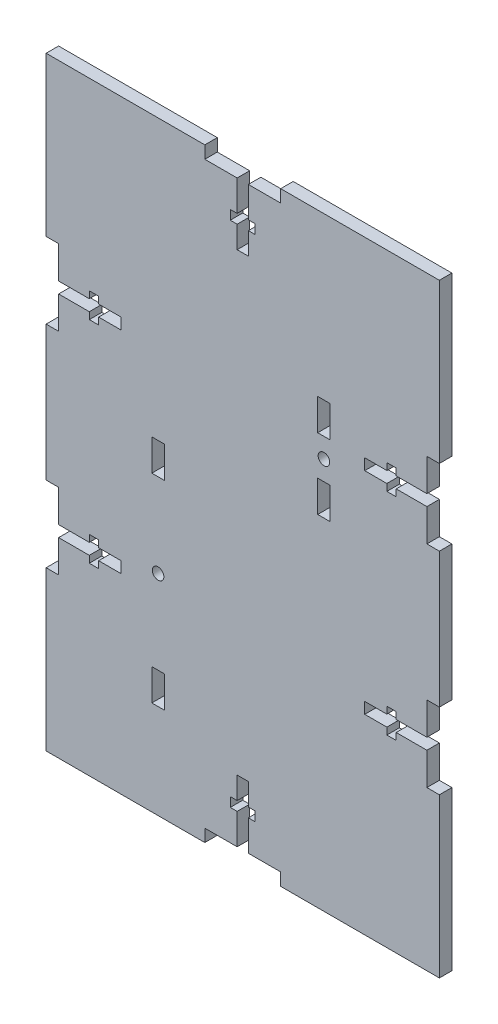
SolidWorks part; units mm, degrees
ref_plane "Front Plane" through (0, 0, 0) normal (0, 0, 1) x (1, 0, 0)
ref_plane "Top Plane" through (0, 0, 0) normal (0, 1, 0) x (1, 0, 0)
ref_plane "Right Plane" through (0, 0, 0) normal (1, 0, 0) x (0, 0, -1)
sketch "Sketch1" plane through (0, 0, 0) normal (0, 0, 1) x (1, 0, 0)
  line L0 (-50, 76.825) -> (-16.6667, 76.825)
  line L1 (-50, -76.825) -> (50, -76.825)
  line L2 (-50, -76.825) -> (-50, 76.825)
  line L3 (-50, 76.825) -> (50, 76.825) construction
  line L4 (50, -76.825) -> (50, 76.825)
  line L5 (-50, -76.825) -> (50, 76.825) construction
  line L6 (-50, 76.825) -> (50, -76.825) construction
  line L7 (-16.6667, 76.825) -> (16.6667, 76.825)
  line L8 (16.6667, 76.825) -> (50, 76.825)
  point P0 (0, 0)
  dimension "D1" = 100
  dimension "D2" = 153.65
extrude "Boss-Extrude1" add sketch "Sketch1" along normal blind 3.18
sketch "Sketch3" [suppressed] plane through (0, 0, 0) normal (0, 0, -1) x (-1, 0, 0)
  line L0 (-32.675, 34.075) -> (-32.675, -61.675)
  line L1 (-32.675, -61.675) -> (32.675, -61.675)
  line L2 (32.675, -61.675) -> (32.675, 34.075)
  line L3 (32.675, 34.075) -> (9.5, 34.075)
  line L4 (9.5, 34.075) -> (9.5, 37.075)
  line L5 (9.5, 37.075) -> (-9.5, 37.075)
  line L6 (-9.5, 37.075) -> (-9.5, 34.075)
  line L7 (-9.5, 34.075) -> (-32.675, 34.075)
  line L8 (32.675, 44.075) -> (-32.675, 44.075)
  line L9 (32.675, -61.675) -> (32.675, 44.075)
  line L10 (-32.675, -61.675) -> (32.675, -61.675)
  line L11 (-32.675, 44.075) -> (-32.675, -61.675)
  line L12 (-32.675, -61.675) -> (-32.675, -73.645) construction
  line L13 (44.645, -73.645) -> (-44.645, -73.645) construction
  line L14 (-32.675, -61.675) -> (-44.645, -61.675) construction
  line L15 (-44.645, -73.645) -> (-44.645, 73.645) construction
  line L16 (32.675, -61.675) -> (44.645, -61.675) construction
  line L17 (44.645, 73.645) -> (44.645, -73.645) construction
  dimension "D1" = 65.35
  dimension "D2" = 95.75
  dimension "D3" = 105.75
  dimension "D4" = 19
  dimension "D5" = 3
extrude "Cut-Extrude1" [suppressed] cut sketch "Sketch3" against normal through all contours L6 L7 L0 L1 L2 L3 L4 L5
sketch "Sketch9" [suppressed] plane through (-44.645, 0, 0) normal (-1, 0, 0) x (0, 0, 1)
  line L0 (0, 0) -> (3.18, 0) construction
  line L1 (0, 50) -> (0, -50) construction
  line L2 (3.18, 50) -> (3.18, -50) construction
  line L4 (0, -9.65) -> (3.18, -9.65)
  line L5 (0, -9.65) -> (0, 9.65)
  line L6 (0, 9.65) -> (3.18, 9.65)
  line L7 (3.18, -9.65) -> (3.18, 9.65)
  line L8 (0, -9.65) -> (3.18, 9.65) construction
  line L9 (0, 9.65) -> (3.18, -9.65) construction
  point P6 (1.59, 0)
  dimension "D1" = 19.3
extrude "Boss-Extrude4" [suppressed] add sketch "Sketch9" along normal blind 3.18
sketch "Sketch10" [suppressed] plane through (0, 0, 3.18) normal (0, 0, 1) x (1, 0, 0)
  line L0 (-46.235, 9.65) -> (-46.235, -9.65) construction
  line L1 (-47.825, 9.65) -> (-44.645, 9.65) construction
  line L2 (-47.825, -9.65) -> (-44.645, -9.65) construction
  circle A0 centre (-46.235, 0) radius 1.425
extrude "Cut-Extrude4" [suppressed] cut sketch "Sketch10" against normal through all
mirror "Mirror1" [suppressed] about plane through (0, 0, 0) normal (1, 0, 0)
sketch "Sketch18" [suppressed] plane through (44.645, 0, 0) normal (1, 0, 0) x (0, 0, -1)
  line L0 (0, 0) -> (-3.18, 0) construction
  line L1 (0, -50) -> (0, 50) construction
  line L2 (-3.18, -50) -> (-3.18, 50) construction
  line L4 (-3.18, -9.65) -> (0, -9.65)
  line L5 (-3.18, -9.65) -> (-3.18, 9.65)
  line L6 (-3.18, 9.65) -> (0, 9.65)
  line L7 (0, -9.65) -> (0, 9.65)
  line L8 (-3.18, -9.65) -> (0, 9.65) construction
  line L9 (-3.18, 9.65) -> (0, -9.65) construction
  point P6 (-1.59, 0)
  dimension "D1" = 19.3
extrude "Boss-Extrude8" [suppressed] add sketch "Sketch18" along normal blind 3.18
sketch "Sketch19" [suppressed] plane through (0, 0, 3.18) normal (0, 0, 1) x (1, 0, 0)
  line L0 (46.235, -9.65) -> (46.235, 9.65) construction
  line L1 (47.825, -9.65) -> (44.645, -9.65) construction
  line L2 (47.825, 9.65) -> (44.645, 9.65) construction
  circle A0 centre (46.235, 0) radius 1.425
extrude "Cut-Extrude8" [suppressed] cut sketch "Sketch19" against normal through all
mirror "Mirror2" [suppressed] about plane through (0, 0, 0) normal (1, 0, 0)
sketch "Sketch20" plane through (0, 0, 3.18) normal (0, 0, 1) x (1, 0, 0)
  line L0 (0, 70.465) -> (0, 0) construction
  line L1 (50, 76.825) -> (-50, 76.825) construction
  line L2 (-9.65, 76.825) -> (9.65, 76.825)
  line L3 (9.65, 76.825) -> (9.65, 73.645)
  line L4 (9.65, 73.645) -> (1.425, 73.645)
  line L5 (1.425, 73.645) -> (1.425, 65.845)
  line L6 (1.425, 65.845) -> (3.175, 65.845)
  line L7 (3.175, 65.845) -> (3.175, 63.465)
  line L8 (3.175, 63.465) -> (1.425, 63.465)
  line L9 (1.425, 63.465) -> (1.425, 57.845)
  line L10 (1.425, 57.845) -> (-1.425, 57.845)
  line L11 (-1.425, 57.845) -> (-1.425, 63.465)
  line L12 (-1.425, 63.465) -> (-3.175, 63.465)
  line L13 (-3.175, 63.465) -> (-3.175, 65.845)
  line L14 (-3.175, 65.845) -> (-1.425, 65.845)
  line L15 (-1.425, 65.845) -> (-1.425, 73.645)
  line L16 (-1.425, 73.645) -> (-9.65, 73.645)
  line L17 (-9.65, 73.645) -> (-9.65, 76.825)
  dimension "D1" = 19.3
  dimension "D2" = 3.18
  dimension "D3" = 15.8
  dimension "D4" = 6.35
  dimension "D5" = 2.38
  dimension "D6" = 2.85
  dimension "D7" = 7.8
extrude "Cut-Extrude9" cut sketch "Sketch20" against normal through all
mirror "Mirror3" about plane through (0, 0, 0) normal (0, 1, 0) of "Cut-Extrude9"
sketch "Sketch23" plane through (0, 0, 3.18) normal (0, 0, 1) x (1, 0, 0)
  line L0 (-50, 17.175) -> (-50, 36.475)
  line L1 (-50, 76.825) -> (-50, -76.825) construction
  line L2 (-50, 36.475) -> (-46.82, 36.475)
  line L3 (-46.82, 36.475) -> (-46.82, 28.25)
  line L4 (-46.82, 28.25) -> (-39.02, 28.25)
  line L5 (-39.02, 28.25) -> (-39.02, 30)
  line L6 (-39.02, 30) -> (-36.64, 30)
  line L7 (-36.64, 30) -> (-36.64, 28.25)
  line L8 (-36.64, 28.25) -> (-31.02, 28.25)
  line L9 (-31.02, 28.25) -> (-31.02, 25.4)
  line L10 (-31.02, 25.4) -> (-36.64, 25.4)
  line L11 (-36.64, 25.4) -> (-36.64, 23.65)
  line L12 (-36.64, 23.65) -> (-39.02, 23.65)
  line L13 (-39.02, 23.65) -> (-39.02, 25.4)
  line L14 (-39.02, 25.4) -> (-46.82, 25.4)
  line L15 (-46.82, 25.4) -> (-46.82, 17.175)
  line L16 (-46.82, 17.175) -> (-50, 17.175)
  line L17 (-9.65, 76.825) -> (-50, 76.825) construction
  line L19 (-31.02, 26.825) -> (-50, 26.825) construction
  line L20 (-50, -36.475) -> (-50, -17.175)
  line L21 (-50, -17.175) -> (-46.82, -17.175)
  line L22 (-46.82, -17.175) -> (-46.82, -25.4)
  line L23 (-46.82, -25.4) -> (-39.02, -25.4)
  line L24 (-39.02, -25.4) -> (-39.02, -23.65)
  line L25 (-39.02, -23.65) -> (-36.64, -23.65)
  line L26 (-36.64, -23.65) -> (-36.64, -25.4)
  line L27 (-36.64, -25.4) -> (-31.02, -25.4)
  line L28 (-31.02, -25.4) -> (-31.02, -28.25)
  line L29 (-31.02, -28.25) -> (-36.64, -28.25)
  line L30 (-36.64, -28.25) -> (-36.64, -30)
  line L31 (-36.64, -30) -> (-39.02, -30)
  line L32 (-39.02, -30) -> (-39.02, -28.25)
  line L33 (-39.02, -28.25) -> (-46.82, -28.25)
  line L34 (-46.82, -28.25) -> (-46.82, -36.475)
  line L35 (-46.82, -36.475) -> (-50, -36.475)
  line L36 (-50, -26.825) -> (-31.02, -26.825) construction
  line L37 (-50, -76.825) -> (-9.65, -76.825) construction
  dimension "D1" = 50
  dimension "D2" = 19.3
  dimension "D3" = 3.18
  dimension "D4" = 15.8
  dimension "D5" = 6.35
  dimension "D6" = 2.85
  dimension "D7" = 7.8
  dimension "D8" = 2.38
  dimension "D9" = 19.3
  dimension "D10" = 3.18
  dimension "D11" = 7.8
  dimension "D12" = 15.8
  dimension "D13" = 6.35
  dimension "D14" = 2.85
  dimension "D15" = 2.38
  dimension "D16" = 50
  dimension "D17" = 1.75
extrude "Cut-Extrude10" cut sketch "Sketch23" against normal through all
sketch "Sketch24" [suppressed] plane through (0, 0, 3.18) normal (0, 0, 1) x (1, 0, 0)
  line L0 (50, -17.175) -> (50, -36.475)
  line L1 (50, -76.825) -> (50, 76.825) construction
  line L2 (50, -36.475) -> (46.82, -36.475)
  line L3 (46.82, -36.475) -> (46.82, -28.25)
  line L4 (46.82, -28.25) -> (39.02, -28.25)
  line L5 (39.02, -28.25) -> (39.02, -30)
  line L6 (39.02, -30) -> (36.64, -30)
  line L7 (36.64, -30) -> (36.64, -28.25)
  line L8 (36.64, -28.25) -> (31.02, -28.25)
  line L9 (31.02, -28.25) -> (31.02, -25.4)
  line L10 (31.02, -25.4) -> (36.64, -25.4)
  line L11 (36.64, -25.4) -> (36.64, -23.65)
  line L12 (36.64, -23.65) -> (39.02, -23.65)
  line L13 (39.02, -23.65) -> (39.02, -25.4)
  line L14 (39.02, -25.4) -> (46.82, -25.4)
  line L15 (46.82, -25.4) -> (46.82, -17.175)
  line L16 (46.82, -17.175) -> (50, -17.175)
  line L17 (31.02, -26.825) -> (50, -26.825) construction
  line L18 (9.65, -76.825) -> (50, -76.825) construction
  line L19 (50, 36.475) -> (50, 17.175)
  line L20 (50, 17.175) -> (46.82, 17.175)
  line L21 (46.82, 17.175) -> (46.82, 25.4)
  line L22 (46.82, 25.4) -> (39.02, 25.4)
  line L23 (39.02, 25.4) -> (39.02, 23.65)
  line L24 (39.02, 23.65) -> (36.64, 23.65)
  line L25 (36.64, 23.65) -> (36.64, 25.4)
  line L26 (36.64, 25.4) -> (31.02, 25.4)
  line L27 (31.02, 25.4) -> (31.02, 28.25)
  line L28 (31.02, 28.25) -> (36.64, 28.25)
  line L29 (36.64, 28.25) -> (36.64, 30)
  line L30 (36.64, 30) -> (39.02, 30)
  line L31 (39.02, 30) -> (39.02, 28.25)
  line L32 (39.02, 28.25) -> (46.82, 28.25)
  line L33 (46.82, 28.25) -> (46.82, 36.475)
  line L34 (46.82, 36.475) -> (50, 36.475)
  line L35 (31.02, 26.825) -> (50, 26.825) construction
  line L36 (50, 76.825) -> (9.65, 76.825) construction
  dimension "D1" = 19.3
  dimension "D2" = 3.18
  dimension "D3" = 15.8
  dimension "D4" = 7.8
  dimension "D5" = 6.35
  dimension "D6" = 2.85
  dimension "D7" = 2.38
  dimension "D8" = 50
  dimension "D9" = 19.3
  dimension "D10" = 3.18
  dimension "D11" = 7.8
  dimension "D12" = 15.8
  dimension "D13" = 6.35
  dimension "D14" = 2.85
  dimension "D15" = 2.38
  dimension "D16" = 50
extrude "Cut-Extrude11" [suppressed] cut sketch "Sketch24" against normal through all
sketch "Sketch25" [suppressed] plane through (0, 0, 3.18) normal (0, 0, 1) x (1, 0, 0)
  line L0 (9.65, -50) -> (-9.65, -50)
  line L1 (-44.645, -50) -> (44.645, -50) construction
  line L2 (-9.65, -50) -> (-9.65, -46.82)
  line L3 (-9.65, -46.82) -> (-1.425, -46.82)
  line L4 (-1.425, -46.82) -> (-1.425, -39.02)
  line L5 (-1.425, -39.02) -> (-3.175, -39.02)
  line L6 (-3.175, -39.02) -> (-3.175, -36.64)
  line L7 (-3.175, -36.64) -> (-1.425, -36.64)
  line L8 (-1.425, -36.64) -> (-1.425, -31.02)
  line L9 (-1.425, -31.02) -> (1.425, -31.02)
  line L10 (1.425, -31.02) -> (1.425, -36.64)
  line L11 (1.425, -36.64) -> (3.175, -36.64)
  line L12 (3.175, -36.64) -> (3.175, -39.02)
  line L13 (3.175, -39.02) -> (1.425, -39.02)
  line L14 (1.425, -39.02) -> (1.425, -46.82)
  line L15 (1.425, -46.82) -> (9.65, -46.82)
  line L16 (9.65, -46.82) -> (9.65, -50)
  line L17 (0, -50) -> (0, 0) construction
  dimension "D1" = 19.3
  dimension "D2" = 3.18
  dimension "D3" = 15.8
  dimension "D4" = 7.8
  dimension "D5" = 6.35
  dimension "D6" = 2.85
  dimension "D7" = 2.38
extrude "Cut-Extrude12" [suppressed] cut sketch "Sketch25" against normal through all
sketch "Sketch26" [suppressed] plane through (0, 0, 3.18) normal (0, 0, 1) x (1, 0, 0)
  line L0 (-9.65, 50) -> (9.65, 50)
  line L1 (44.645, 50) -> (-44.645, 50) construction
  line L2 (9.65, 50) -> (9.65, 46.82)
  line L3 (9.65, 46.82) -> (1.425, 46.82)
  line L4 (1.425, 46.82) -> (1.425, 39.02)
  line L5 (1.425, 39.02) -> (3.175, 39.02)
  line L6 (3.175, 39.02) -> (3.175, 36.64)
  line L7 (3.175, 36.64) -> (1.425, 36.64)
  line L8 (1.425, 36.64) -> (1.425, 31.02)
  line L9 (1.425, 31.02) -> (-1.425, 31.02)
  line L10 (-1.425, 31.02) -> (-1.425, 36.64)
  line L11 (-1.425, 36.64) -> (-3.175, 36.64)
  line L12 (-3.175, 36.64) -> (-3.175, 39.02)
  line L13 (-3.175, 39.02) -> (-1.425, 39.02)
  line L14 (-1.425, 39.02) -> (-1.425, 46.82)
  line L15 (-1.425, 46.82) -> (-9.65, 46.82)
  line L16 (-9.65, 46.82) -> (-9.65, 50)
  line L17 (0, 50) -> (0, -4.4192) construction
  dimension "D1" = 19.3
  dimension "D2" = 3.18
  dimension "D3" = 7.8
  dimension "D4" = 15.8
  dimension "D5" = 6.35
  dimension "D6" = 2.85
  dimension "D7" = 2.38
extrude "Cut-Extrude13" [suppressed] cut sketch "Sketch26" against normal through all
mirror "Mirror4" about plane through (0, 0, 0) normal (1, 0, 0) of "Cut-Extrude10"
mirror "Mirror5" [suppressed] about plane through (0, 0, 0) normal (1, 0, 0)
mirror "Mirror6" [suppressed] about plane through (0, 0, 0) normal (0, 1, 0)
mirror "Mirror7" [suppressed] about plane through (0, 0, 0) normal (0, 1, 0)
sketch "Sketch27" [suppressed] plane through (-44.645, 0, 0) normal (-1, 0, 0) x (0, 0, 1)
  line L0 (0, -36.475) -> (0, -17.175)
  line L1 (0, 73.645) -> (0, -73.645) construction
  line L2 (0, -17.175) -> (3.18, -17.175)
  line L3 (3.18, 73.645) -> (3.18, -73.645) construction
  line L4 (3.18, -17.175) -> (3.18, -36.475)
  line L5 (3.18, -36.475) -> (0, -36.475)
  line L6 (3.18, -26.825) -> (0, -26.825) construction
  line L7 (3.18, -73.645) -> (0, -73.645) construction
  dimension "D1" = 19.3
  dimension "D2" = 46.82
extrude "Boss-Extrude9" [suppressed] add sketch "Sketch27" along normal blind 3.18
sketch "Sketch28" [suppressed] plane through (0, -73.645, 0) normal (0, -1, 0) x (1, 0, 0)
  line L0 (9.65, 0) -> (-9.65, 0)
  line L1 (-44.645, 0) -> (44.645, 0) construction
  line L2 (-9.65, 0) -> (-9.65, 3.18)
  line L3 (-44.645, 3.18) -> (44.645, 3.18) construction
  line L4 (-9.65, 3.18) -> (9.65, 3.18)
  line L5 (9.65, 3.18) -> (9.65, 0)
  line L6 (0, 0) -> (0, 3.18) construction
  dimension "D1" = 19.3
extrude "Boss-Extrude10" [suppressed] add sketch "Sketch28" along normal blind 3.18
sketch "Sketch29" [suppressed] plane through (0, 0, 3.18) normal (0, 0, 1) x (1, 0, 0)
  line L0 (-47.825, -26.825) -> (-37.3062, -26.825) construction
  line L1 (-47.825, -36.475) -> (-47.825, -17.175) construction
  line L2 (-46.235, -17.175) -> (-46.235, -36.475) construction
  line L3 (-47.825, -17.175) -> (-44.645, -17.175) construction
  line L4 (-47.825, -36.475) -> (-44.645, -36.475) construction
  circle A0 centre (-46.235, -26.825) radius 1.425
extrude "Cut-Extrude14" [suppressed] cut sketch "Sketch29" against normal through all
sketch "Sketch30" [suppressed] plane through (0, 0, 3.18) normal (0, 0, 1) x (1, 0, 0)
  line L0 (0, -76.825) -> (0, -66.2855) construction
  line L1 (9.65, -76.825) -> (-9.65, -76.825) construction
  line L2 (9.65, -75.235) -> (-9.65, -75.235) construction
  line L3 (9.65, -76.825) -> (9.65, -73.645) construction
  line L4 (-9.65, -76.825) -> (-9.65, -73.645) construction
  circle A0 centre (0, -75.235) radius 1.425
extrude "Cut-Extrude15" [suppressed] cut sketch "Sketch30" against normal through all
mirror "Mirror8" [suppressed] about plane through (0, 0, 0) normal (1, 0, 0)
mirror "Mirror9" [suppressed] about plane through (0, 0, 0) normal (0, 1, 0)
sketch "Sketch31" [suppressed] plane through (0, 0, 3.18) normal (0, 0, 1) x (1, 0, 0)
  line L0 (14.341, -8.1358) -> (14.341, -12.6358) construction
  line L8 (5.175, -1.9558) -> (5.175, 19.3642) construction
  line L10 (-24.825, 19.3642) -> (-24.825, -1.9558) construction
  line L11 (5.175, 19.3642) -> (-24.825, 19.3642) construction
  line L16 (23.507, -9.6358) -> (39.341, -9.6358) construction
  line L17 (23.507, 19.3642) -> (23.507, -9.6358) construction
  line L18 (39.341, 19.3642) -> (23.507, 19.3642) construction
  line L19 (39.341, -9.6358) -> (39.341, 19.3642) construction
  line L26 (14.341, -15.8158) -> (14.341, -12.6358) construction
  line L29 (-24.825, -1.9558) -> (5.175, -1.9558) construction
  line L34 (20.5772, -7.1358) -> (20.5772, 11.3642) construction
  line L35 (20.5772, 11.3642) -> (8.1048, 11.3642) construction
  line L36 (8.1048, 11.3642) -> (8.1048, -7.1358) construction
  line L37 (9.7431, -8.1358) -> (18.9389, -8.1358) construction
  line L38 (14.341, -15.8158) -> (14.341, -50) construction
  line L39 (-17.325, 9.65) -> (-24.825, 9.65) construction
  line L40 (-6.159, -12.4758) -> (34.841, -12.4758)
  line L41 (-6.159, -12.4758) -> (-6.159, -15.9758)
  line L42 (-6.159, -15.9758) -> (34.841, -15.9758)
  line L43 (34.841, -12.4758) -> (34.841, -15.9758)
  line L88 (-44.645, -50) -> (-9.65, -50) construction
  line L89 (-9.65, -50) -> (-9.65, -46.82) construction
  line L90 (-9.65, -46.82) -> (-1.425, -46.82) construction
  line L91 (-1.425, -46.82) -> (-1.425, -39.02) construction
  line L92 (-1.425, -39.02) -> (-3.175, -39.02) construction
  line L93 (-3.175, -39.02) -> (-3.175, -36.64) construction
  line L94 (-3.175, -36.64) -> (-1.425, -36.64) construction
  line L95 (-1.425, -36.64) -> (-1.425, -31.02) construction
  line L96 (-1.425, -31.02) -> (1.425, -31.02) construction
  line L97 (1.425, -31.02) -> (1.425, -36.64) construction
  line L98 (1.425, -36.64) -> (3.175, -36.64) construction
  line L99 (3.175, -36.64) -> (3.175, -39.02) construction
  line L100 (3.175, -39.02) -> (1.425, -39.02) construction
  line L101 (1.425, -39.02) -> (1.425, -46.82) construction
  line L102 (1.425, -46.82) -> (9.65, -46.82) construction
  line L103 (9.65, -46.82) -> (9.65, -50) construction
  line L104 (9.65, -50) -> (44.645, -50) construction
  line L105 (44.645, -50) -> (44.645, -9.65) construction
  line L106 (44.645, -9.65) -> (47.825, -9.65) construction
  line L107 (47.825, -9.65) -> (47.825, 9.65) construction
  line L108 (47.825, 9.65) -> (44.645, 9.65) construction
  line L109 (44.645, 9.65) -> (44.645, 50) construction
  line L110 (44.645, 50) -> (9.65, 50) construction
  line L111 (9.65, 50) -> (9.65, 46.82) construction
  line L112 (9.65, 46.82) -> (1.425, 46.82) construction
  line L113 (1.425, 46.82) -> (1.425, 39.02) construction
  line L114 (1.425, 39.02) -> (3.175, 39.02) construction
  line L115 (3.175, 39.02) -> (3.175, 36.64) construction
  line L116 (3.175, 36.64) -> (1.425, 36.64) construction
  line L117 (1.425, 36.64) -> (1.425, 31.02) construction
  line L118 (1.425, 31.02) -> (-1.425, 31.02) construction
  line L119 (-1.425, 31.02) -> (-1.425, 36.64) construction
  line L120 (-1.425, 36.64) -> (-3.175, 36.64) construction
  line L121 (-3.175, 36.64) -> (-3.175, 39.02) construction
  line L122 (-3.175, 39.02) -> (-1.425, 39.02) construction
  line L123 (-1.425, 39.02) -> (-1.425, 46.82) construction
  line L124 (-1.425, 46.82) -> (-9.65, 46.82) construction
  line L125 (-9.65, 46.82) -> (-9.65, 50) construction
  line L126 (-9.65, 50) -> (-44.645, 50) construction
  line L127 (-44.645, 50) -> (-44.645, 9.65) construction
  line L128 (-44.645, 9.65) -> (-47.825, 9.65) construction
  line L129 (-47.825, 9.65) -> (-47.825, -9.65) construction
  line L130 (-47.825, -9.65) -> (-44.645, -9.65) construction
  line L131 (-44.645, -9.65) -> (-44.645, -50) construction
  line L132 (-6.159, -12.4758) -> (34.841, -15.9758) construction
  line L133 (-6.159, -15.9758) -> (34.841, -12.4758) construction
  line L134 (-17.325, 9.65) -> (-17.325, -1.9558) construction
  line L135 (31.3061, 4.8642) -> (39.341, 4.8642) construction
  line L136 (31.3061, 4.8642) -> (31.3061, 19.3642) construction
  line L137 (-17.325, 9.65) -> (-4.325, 9.65) construction
  circle A0 centre (-17.325, 9.65) radius 1.5
  circle A1 centre (31.3061, 4.8642) radius 1.5
  circle A2 centre (-4.325, 9.65) radius 1.5
  spline S4 degree 3 poles (8.1048, -7.1358) (8.1048, -7.3148) (8.1799, -7.485) (8.4092, -7.7556) (8.5582, -7.8571) (8.8762, -8.0081) (9.0479, -8.0586) (9.3919, -8.1221) (9.5665, -8.1358) (9.7431, -8.1358) knots 0 0 0 0 0.25 0.25 0.5 0.5 0.75 0.75 1 1 1 1 construction
  spline S5 degree 3 poles (18.9389, -8.1358) (19.1156, -8.1358) (19.2906, -8.1221) (19.6363, -8.0581) (19.8071, -8.0076) (20.1239, -7.857) (20.2729, -7.7556) (20.5025, -7.4843) (20.5772, -7.3148) (20.5772, -7.1358) knots 0 0 0 0 0.25 0.25 0.5 0.5 0.75 0.75 1 1 1 1 construction
  point P14 (14.341, -14.2258)
  point P46 (-44.645, 50)
  dimension "D6" = 3
  dimension "D4" = 41
  dimension "D5" = 3.5
  dimension "D7" = 7.5
  dimension "D9" = 13
extrude "Cut-Extrude16" [suppressed] cut sketch "Sketch31" against normal through all contours L41 L40 L43 L42 | A1 | A2 | A0
sketch "Sketch32" plane through (0, 0, 3.18) normal (0, 0, 1) x (1, 0, 0)
  line L0 (22.24, 17.7829) -> (22.24, 9.7829)
  line L1 (22.24, 35.7829) -> (22.24, 27.7829)
  line L2 (22.24, 35.7829) -> (19.06, 35.7829)
  line L3 (22.24, 35.7829) -> (22.24, 27.7829)
  line L4 (22.24, 27.7829) -> (19.06, 27.7829)
  line L5 (19.06, 35.7829) -> (19.06, 27.7829)
  line L6 (22.24, 17.7829) -> (19.06, 17.7829)
  line L7 (22.24, 17.7829) -> (22.24, 9.7829)
  line L8 (22.24, 9.7829) -> (19.06, 9.7829)
  line L9 (19.06, 17.7829) -> (19.06, 9.7829)
  line L10 (22.24, 17.7829) -> (22.24, 27.7829) construction
  line L11 (50, -17.175) -> (50, 17.175) construction
  line L12 (50, 17.175) -> (46.82, 17.175) construction
  line L13 (46.82, 17.175) -> (46.82, 25.4) construction
  line L14 (46.82, 25.4) -> (39.02, 25.4) construction
  line L15 (39.02, 25.4) -> (39.02, 23.65) construction
  line L16 (39.02, 23.65) -> (36.64, 23.65) construction
  line L17 (36.64, 23.65) -> (36.64, 25.4) construction
  line L18 (36.64, 25.4) -> (31.02, 25.4) construction
  line L19 (31.02, 25.4) -> (31.02, 28.25) construction
  line L20 (31.02, 28.25) -> (36.64, 28.25) construction
  line L21 (36.64, 28.25) -> (36.64, 30) construction
  line L22 (36.64, 30) -> (39.02, 30) construction
  line L23 (39.02, 30) -> (39.02, 28.25) construction
  line L24 (39.02, 28.25) -> (46.82, 28.25) construction
  line L25 (46.82, 28.25) -> (46.82, 36.475) construction
  line L26 (46.82, 36.475) -> (50, 36.475) construction
  line L27 (50, 36.475) -> (50, 76.825) construction
  line L28 (50, 76.825) -> (9.65, 76.825) construction
  line L29 (9.65, 76.825) -> (9.65, 73.645) construction
  line L30 (9.65, 73.645) -> (1.425, 73.645) construction
  line L31 (1.425, 73.645) -> (1.425, 65.845) construction
  line L32 (1.425, 65.845) -> (3.175, 65.845) construction
  line L33 (3.175, 65.845) -> (3.175, 63.465) construction
  line L34 (3.175, 63.465) -> (1.425, 63.465) construction
  line L35 (1.425, 63.465) -> (1.425, 57.845) construction
  line L36 (1.425, 57.845) -> (-1.425, 57.845) construction
  line L37 (-1.425, 57.845) -> (-1.425, 63.465) construction
  line L38 (-1.425, 63.465) -> (-3.175, 63.465) construction
  line L39 (-3.175, 63.465) -> (-3.175, 65.845) construction
  line L40 (-3.175, 65.845) -> (-1.425, 65.845) construction
  line L41 (-1.425, 65.845) -> (-1.425, 73.645) construction
  line L42 (-1.425, 73.645) -> (-9.65, 73.645) construction
  line L43 (-9.65, 73.645) -> (-9.65, 76.825) construction
  line L44 (-9.65, 76.825) -> (-50, 76.825) construction
  line L45 (-50, 76.825) -> (-50, 36.475) construction
  line L46 (-50, 36.475) -> (-46.82, 36.475) construction
  line L47 (-46.82, 36.475) -> (-46.82, 28.25) construction
  line L48 (-46.82, 28.25) -> (-39.02, 28.25) construction
  line L49 (-39.02, 28.25) -> (-39.02, 30) construction
  line L50 (-39.02, 30) -> (-36.64, 30) construction
  line L51 (-36.64, 30) -> (-36.64, 28.25) construction
  line L52 (-36.64, 28.25) -> (-31.02, 28.25) construction
  line L53 (-31.02, 28.25) -> (-31.02, 25.4) construction
  line L54 (-31.02, 25.4) -> (-36.64, 25.4) construction
  line L55 (-36.64, 25.4) -> (-36.64, 23.65) construction
  line L56 (-36.64, 23.65) -> (-39.02, 23.65) construction
  line L57 (-39.02, 23.65) -> (-39.02, 25.4) construction
  line L58 (-39.02, 25.4) -> (-46.82, 25.4) construction
  line L59 (-46.82, 25.4) -> (-46.82, 17.175) construction
  line L60 (-46.82, 17.175) -> (-50, 17.175) construction
  line L61 (-50, 17.175) -> (-50, -17.175) construction
  line L62 (-50, -17.175) -> (-46.82, -17.175) construction
  line L63 (-46.82, -17.175) -> (-46.82, -25.4) construction
  line L64 (-46.82, -25.4) -> (-39.02, -25.4) construction
  line L65 (-39.02, -25.4) -> (-39.02, -23.65) construction
  line L66 (-39.02, -23.65) -> (-36.64, -23.65) construction
  line L67 (-36.64, -23.65) -> (-36.64, -25.4) construction
  line L68 (-36.64, -25.4) -> (-31.02, -25.4) construction
  line L69 (-31.02, -25.4) -> (-31.02, -28.25) construction
  line L70 (-31.02, -28.25) -> (-36.64, -28.25) construction
  line L71 (-36.64, -28.25) -> (-36.64, -30) construction
  line L72 (-36.64, -30) -> (-39.02, -30) construction
  line L73 (-39.02, -30) -> (-39.02, -28.25) construction
  line L74 (-39.02, -28.25) -> (-46.82, -28.25) construction
  line L75 (-46.82, -28.25) -> (-46.82, -36.475) construction
  line L76 (-46.82, -36.475) -> (-50, -36.475) construction
  line L77 (-50, -36.475) -> (-50, -76.825) construction
  line L78 (-50, -76.825) -> (-9.65, -76.825) construction
  line L79 (-9.65, -76.825) -> (-9.65, -73.645) construction
  line L80 (-9.65, -73.645) -> (-1.425, -73.645) construction
  line L81 (-1.425, -73.645) -> (-1.425, -65.845) construction
  line L82 (-1.425, -65.845) -> (-3.175, -65.845) construction
  line L83 (-3.175, -65.845) -> (-3.175, -63.465) construction
  line L84 (-3.175, -63.465) -> (-1.425, -63.465) construction
  line L85 (-1.425, -63.465) -> (-1.425, -57.845) construction
  line L86 (-1.425, -57.845) -> (1.425, -57.845) construction
  line L87 (1.425, -57.845) -> (1.425, -63.465) construction
  line L88 (1.425, -63.465) -> (3.175, -63.465) construction
  line L89 (3.175, -63.465) -> (3.175, -65.845) construction
  line L90 (3.175, -65.845) -> (1.425, -65.845) construction
  line L91 (1.425, -65.845) -> (1.425, -73.645) construction
  line L92 (1.425, -73.645) -> (9.65, -73.645) construction
  line L93 (9.65, -73.645) -> (9.65, -76.825) construction
  line L94 (9.65, -76.825) -> (50, -76.825) construction
  line L95 (50, -76.825) -> (50, -36.475) construction
  line L96 (50, -36.475) -> (46.82, -36.475) construction
  line L97 (46.82, -36.475) -> (46.82, -28.25) construction
  line L98 (46.82, -28.25) -> (39.02, -28.25) construction
  line L99 (39.02, -28.25) -> (39.02, -30) construction
  line L100 (39.02, -30) -> (36.64, -30) construction
  line L101 (36.64, -30) -> (36.64, -28.25) construction
  line L102 (36.64, -28.25) -> (31.02, -28.25) construction
  line L103 (31.02, -28.25) -> (31.02, -25.4) construction
  line L104 (31.02, -25.4) -> (36.64, -25.4) construction
  line L105 (36.64, -25.4) -> (36.64, -23.65) construction
  line L106 (36.64, -23.65) -> (39.02, -23.65) construction
  line L107 (39.02, -23.65) -> (39.02, -25.4) construction
  line L108 (39.02, -25.4) -> (46.82, -25.4) construction
  line L109 (46.82, -25.4) -> (46.82, -17.175) construction
  line L110 (46.82, -17.175) -> (50, -17.175) construction
  line L111 (20.65, 27.7829) -> (20.65, 17.7829) construction
  line L112 (0, 0) -> (0, 57.845) construction
  line L113 (-20.65, 27.7829) -> (-20.65, 17.7829) construction
  line L114 (-22.24, 17.7829) -> (-22.24, 27.7829) construction
  line L115 (-19.06, 17.7829) -> (-19.06, 9.7829)
  line L116 (-22.24, 9.7829) -> (-19.06, 9.7829)
  line L117 (-22.24, 17.7829) -> (-22.24, 9.7829)
  line L118 (-22.24, 17.7829) -> (-19.06, 17.7829)
  line L119 (-19.06, 35.7829) -> (-19.06, 27.7829)
  line L120 (-22.24, 27.7829) -> (-19.06, 27.7829)
  line L121 (-22.24, 35.7829) -> (-22.24, 27.7829)
  line L122 (-22.24, 35.7829) -> (-19.06, 35.7829)
  line L123 (-22.24, 35.7829) -> (-22.24, 27.7829)
  line L124 (-22.24, 17.7829) -> (-22.24, 9.7829)
  circle A0 centre (20.65, 22.7829) radius 1.47
  circle A1 centre (-20.65, 22.7829) radius 1.47
  dimension "D1" = 2.94
extrude "Cut-Extrude17" [suppressed] cut sketch "Sketch32" against normal through all contours L118 L117 L116 L115 | L122 L121 L120 L119 | A1
extrude "Cut-Extrude18" cut sketch "Sketch32<4>" against normal through all contours L2 L5 L4 L1 | A0 | L6 L9 L8 L0 region at (20.65, 13.7829, 3.18) region at (20.65, 31.7829, 3.18) region at (20.65, 22.7829, 3.18)
sketch "Sketch32<4>" plane through (0, 0, 3.18) normal (0, 0, 1) x (1, 0, 0) same geometry as "Sketch32"
sketch "Sketch33" plane through (0, 0, 0) normal (0, 0, 1) x (1, 0, 0)
  line L0 (0, -1.749) -> (0, 1.749) construction
  line L1 (19.94, 5.7884) -> (23.12, 5.7884)
  line L2 (19.94, -2.2116) -> (19.94, 5.7884)
  line L3 (23.12, -2.2116) -> (19.94, -2.2116)
  line L4 (23.12, 5.7884) -> (23.12, -2.2116)
  line L5 (19.94, -44.8116) -> (23.12, -44.8116)
  line L6 (19.94, -52.8116) -> (19.94, -44.8116)
  line L7 (23.12, -52.8116) -> (19.94, -52.8116)
  line L8 (23.12, -44.8116) -> (23.12, -52.8116)
  line L9 (-21.53, -2.2116) -> (-21.53, -44.8116) construction
  line L10 (21.53, -2.2116) -> (21.53, -44.8116) construction
  line L108 (-23.12, -44.8116) -> (-23.12, -52.8116)
  line L109 (-23.12, -52.8116) -> (-19.94, -52.8116)
  line L110 (-19.94, -52.8116) -> (-19.94, -44.8116)
  line L111 (-19.94, -44.8116) -> (-23.12, -44.8116)
  line L112 (-23.12, 5.7884) -> (-23.12, -2.2116)
  line L113 (-23.12, -2.2116) -> (-19.94, -2.2116)
  line L114 (-19.94, -2.2116) -> (-19.94, 5.7884)
  line L115 (-19.94, 5.7884) -> (-23.12, 5.7884)
  circle A0 centre (-21.53, -23.5116) radius 1.47
  circle A1 centre (21.53, -23.5116) radius 1.47
extrude "Cut-Extrude22" [suppressed] cut sketch "Sketch33" along normal through all contours L6 L5 L8 L7 | A1 | L4 L3 L2 L1
sketch "Sketch35" [suppressed] plane through (0, 0, 0) normal (0, 0, 1) x (-1, 0, 0)
  line L2 (17.677, 7.8541) -> (5.677, 7.8603)
  line L3 (17.6824, 18.354) -> (17.677, 7.8541)
  line L5 (5.6824, 18.3603) -> (17.6824, 18.354)
  line L7 (5.677, 7.8603) -> (5.6824, 18.3603)
extrude "Cut-Extrude26" [suppressed] cut sketch "Sketch35" along normal through all
sketch "Sketch36" [suppressed] plane through (0, 0, 3.18) normal (0, 0, 1) x (1, 0, 0)
  line L0 (-36.1816, -36.7568) -> (-21.1816, -36.7568) construction
  line L1 (-33.6816, -34.2568) -> (-23.6816, -34.2568)
  line L2 (-33.6816, -34.2568) -> (-33.6816, -39.2568)
  line L3 (-33.6816, -39.2568) -> (-23.6816, -39.2568)
  line L4 (-23.6816, -34.2568) -> (-23.6816, -39.2568)
  line L5 (-33.6816, -34.2568) -> (-23.6816, -39.2568) construction
  line L6 (-33.6816, -39.2568) -> (-23.6816, -34.2568) construction
  circle A0 centre (-21.1816, -36.7568) radius 1
  circle A1 centre (-36.1816, -36.7568) radius 1
  point P0 (-28.6816, -36.7568)
  point P8 (-28.6816, -36.7568)
  dimension "D4" = 2
  dimension "D1" = 10
  dimension "D2" = 5
  dimension "D3" = 15
extrude "Cut-Extrude27" [suppressed] cut sketch "Sketch36" against normal through all
extrude "Cut-Extrude29" cut sketch "Sketch33<3>" along normal through all contours A0 | L114 L115 L112 L113 | L110 L111 L108 L109 region at (-21.53, -48.8116, 0) region at (-21.53, 1.7884, 0) region at (-21.53, -23.5116, 0)
sketch "Sketch33<3>" plane through (0, 0, 0) normal (0, 0, 1) x (1, 0, 0) same geometry as "Sketch33"
